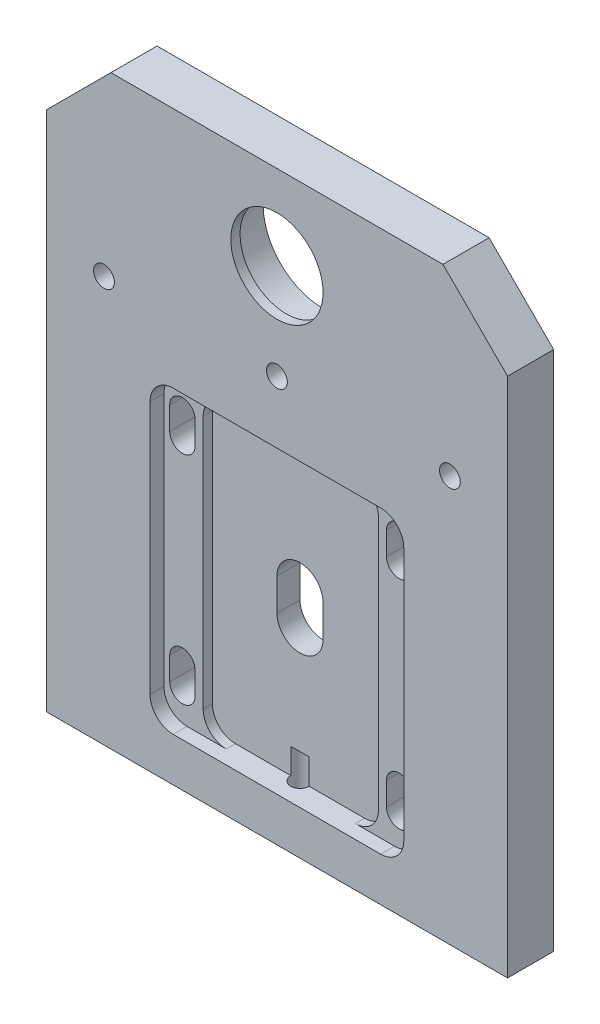
SolidWorks part; units mm, degrees
ref_plane "Piano frontale" through (0, 0, 0) normal (0, 0, 1) x (1, 0, 0)
ref_plane "Piano superiore" through (0, 0, 0) normal (0, 1, 0) x (1, 0, 0)
ref_plane "Piano destro" through (0, 0, 0) normal (1, 0, 0) x (0, 0, -1)
sketch "Schizzo1" plane through (0, 0, 0) normal (0, 0, 1) x (1, 0, 0)
  line L0 (0, 113) -> (14, 127)
  line L1 (0, 0) -> (100, 0)
  line L2 (0, 0) -> (0, 113)
  line L3 (14, 127) -> (86, 127)
  line L4 (100, 0) -> (100, 113)
  line L5 (86, 127) -> (100, 113)
  point P1 (100, 127)
  point P2 (0, 127)
  dimension "D1" = 127
  dimension "D2" = 100
extrude "Estrusione-Estrusione1" add sketch "Schizzo1" against normal blind 10
sketch "Schizzo2" plane through (0, 0, 0) normal (0, 0, 1) x (1, 0, 0)
  line L0 (86, 127) -> (14, 127) construction
  line L2 (50, 0) -> (50, 127) construction
  line L3 (0, 0) -> (100, 0) construction
  circle A0 centre (50, 108.7) radius 10
  dimension "D2" = 20
  dimension "D1" = 18.3
extrude "Taglio-Estrusione1" cut sketch "Schizzo2" against normal blind 10
sketch "Schizzo3" plane through (0, 0, 0) normal (0, 0, 1) x (1, 0, 0)
  line L0 (86, 127) -> (14, 127) construction
  line L1 (95, 88) -> (0, 88) construction
  line L2 (0, 0) -> (100, 0) construction
  line L3 (0, 113) -> (0, 0) construction
  line L6 (50, 0) -> (50, 127) construction
  circle A0 centre (12.5, 88) radius 2.25
  circle A1 centre (50, 88) radius 2.25
  circle A2 centre (87.5, 88) radius 2.25
  dimension "D5" = 4.5
  dimension "D1" = 37.5
  dimension "D2" = 88
extrude "Taglio-Estrusione2" cut sketch "Schizzo3" against normal blind 10
sketch "Schizzo4" plane through (0, 0, 0) normal (0, 0, 1) x (1, 0, 0)
  line L0 (50, 0) -> (50, 127) construction
  line L1 (0, 0) -> (100, 0) construction
  line L2 (0, 88.7572) -> (0, -18.8818) construction
  line L3 (0, 113) -> (0, 0) construction
  line L4 (86, 127) -> (14, 127) construction
  line L8 (27.5, 74.5) -> (72.5, 74.5)
  line L9 (22.5, 69.5) -> (22.5, 14.5)
  line L10 (27.5, 9.5) -> (72.5, 9.5)
  line L11 (77.5, 69.5) -> (77.5, 14.5)
  arc A0 (22.5, 14.5) -> (27.5, 9.5) centre (27.5, 14.5) ccw
  arc A1 (72.5, 9.5) -> (77.5, 14.5) centre (72.5, 14.5) ccw
  arc A2 (77.5, 69.5) -> (72.5, 74.5) centre (72.5, 69.5) ccw
  arc A3 (27.5, 74.5) -> (22.5, 69.5) centre (27.5, 69.5) ccw
  point P23 (77.5, 9.5)
  point P28 (22.5, 74.5)
  dimension "D5" = 5
  dimension "D1" = 45
extrude "Taglio-Estrusione3" cut sketch "Schizzo4" against normal blind 3
sketch "Schizzo5" plane through (0, 0, -3) normal (0, 0, 1) x (1, 0, 0)
  line L0 (0, 0) -> (0, -14.3774) construction
  line L1 (50, 0) -> (50, 127) construction
  line L2 (0, 0) -> (100, 0) construction
  line L3 (86, 127) -> (14, 127) construction
  line L7 (27.5, 9.5) -> (72.5, 9.5) construction
  line L8 (36, 74.5) -> (64, 74.5)
  line L9 (31, 69.5) -> (31, 14.5)
  line L10 (36, 9.5) -> (64, 9.5)
  line L11 (69, 69.5) -> (69, 14.5)
  arc A0 (31, 14.5) -> (36, 9.5) centre (36, 14.5) ccw
  arc A1 (64, 9.5) -> (69, 14.5) centre (64, 14.5) ccw
  arc A2 (64, 74.5) -> (69, 69.5) centre (64, 69.5) cw
  arc A3 (36, 74.5) -> (31, 69.5) centre (36, 69.5) ccw
  point P21 (69, 9.5)
  dimension "D3" = 5
  dimension "D1" = 38
  dimension "D2" = 65
extrude "Taglio-Estrusione4" cut sketch "Schizzo5" against normal blind 2
sketch "Schizzo6" plane through (0, 0, -5) normal (0, 0, 1) x (1, 0, 0)
  line L0 (31, 42) -> (69, 42) construction
  line L1 (31, 69.5) -> (31, 14.5) construction
  line L2 (69, 14.5) -> (69, 69.5) construction
  line L3 (50, 74.5) -> (50, 9.5) construction
  line L4 (64, 74.5) -> (36, 74.5) construction
  line L5 (36, 9.5) -> (64, 9.5) construction
  line L6 (50, 45.5) -> (50, 38.5) construction
  line L13 (54.9932, 45.5) -> (54.9932, 38.5)
  line L14 (45.0068, 45.5) -> (45.0068, 38.5)
  arc A0 (54.9932, 45.5) -> (45.0068, 45.5) centre (50, 45.5) ccw
  arc A1 (45.0068, 38.5) -> (54.9932, 38.5) centre (50, 38.5) ccw
  point P12 (50, 42)
  point P19 (50, 42)
  dimension "D3" = 29
  dimension "D1" = 4.9932
  dimension "D2" = 7
  dimension "D4" = 4.9932
extrude "Taglio-Estrusione5" cut sketch "Schizzo6" against normal through all
sketch "Schizzo7" plane through (0, 0, -3) normal (0, 0, 1) x (1, 0, 0)
  line L0 (22.5, 42) -> (31, 42) construction
  line L1 (22.5, 69.5) -> (22.5, 14.5) construction
  line L2 (31, 69.5) -> (31, 14.5) construction
  line L3 (26.5, 63) -> (26.5, 68) construction
  line L4 (31, 42) -> (69, 42) construction
  line L5 (26.5, 65.5) -> (73.5, 65.5) construction
  line L6 (26.5, 65.5) -> (26.5, 18.5) construction
  line L7 (26.5, 18.5) -> (73.5, 18.5) construction
  line L8 (73.5, 65.5) -> (73.5, 18.5) construction
  line L9 (26.5, 65.5) -> (73.5, 18.5) construction
  line L10 (26.5, 18.5) -> (73.5, 65.5) construction
  line L11 (69, 14.5) -> (69, 69.5) construction
  line L12 (50, 42) -> (50, 0) construction
  line L13 (23.75, 63) -> (23.75, 68)
  line L14 (29.25, 63) -> (29.25, 68)
  line L15 (73.5, 63) -> (73.5, 68) construction
  line L16 (70.75, 63) -> (70.75, 68)
  line L17 (76.25, 63) -> (76.25, 68)
  line L18 (26.5, 16) -> (26.5, 21) construction
  line L19 (23.75, 16) -> (23.75, 21)
  line L20 (29.25, 16) -> (29.25, 21)
  line L21 (73.5, 16) -> (73.5, 21) construction
  line L22 (70.75, 16) -> (70.75, 21)
  line L23 (76.25, 16) -> (76.25, 21)
  line L24 (0, 0) -> (100, 0) construction
  arc A0 (23.75, 63) -> (29.25, 63) centre (26.5, 63) ccw
  arc A1 (29.25, 68) -> (23.75, 68) centre (26.5, 68) ccw
  arc A2 (70.75, 63) -> (76.25, 63) centre (73.5, 63) ccw
  arc A3 (76.25, 68) -> (70.75, 68) centre (73.5, 68) ccw
  arc A4 (23.75, 16) -> (29.25, 16) centre (26.5, 16) ccw
  arc A5 (29.25, 21) -> (23.75, 21) centre (26.5, 21) ccw
  arc A6 (70.75, 16) -> (76.25, 16) centre (73.5, 16) ccw
  arc A7 (76.25, 21) -> (70.75, 21) centre (73.5, 21) ccw
  point P8 (50, 42)
  point P18 (26.5, 65.5)
  point P25 (73.5, 65.5)
  point P31 (26.5, 18.5)
  point P38 (73.5, 18.5)
  dimension "D1" = 47
  dimension "D2" = 47
extrude "Taglio-Estrusione6" cut sketch "Schizzo7" against normal through all
sketch "Schizzo8" plane through (0, 0, -10) normal (0, 0, -1) x (-1, 0, 0)
  circle A0 centre (-50, 108.7) radius 13
  dimension "D1" = 26
extrude "Taglio-Estrusione7" cut sketch "Schizzo8" against normal blind 8
sketch "Schizzo9" plane through (0, 0, -10) normal (0, 0, -1) x (-1, 0, 0)
  circle A0 centre (-85, 83) radius 4
  circle A1 centre (-50, 88) radius 4
  circle A2 centre (-12.5, 88) radius 4
  dimension "D1" = 8
  dimension "D2" = 8
  dimension "D3" = 8
extrude "Taglio-Estrusione8" cut sketch "Schizzo9" against normal blind 4
sketch "Schizzo10" plane through (0, 0, 0) normal (0, -1, 0) x (1, 0, 0)
  line L0 (50, 0) -> (50, -10) construction
  line L4 (0, 0) -> (100, 0) construction
  line L9 (0, -10) -> (100, -10) construction
  line L10 (100, -5) -> (0, -5) construction
  line L11 (100, -10) -> (100, 0) construction
  circle A0 centre (50, -5) radius 2
  circle A1 centre (19.5, -5) radius 2
  circle A2 centre (80.5, -5) radius 2
  dimension "D1" = 4
  dimension "D2" = 4
  dimension "D3" = 30.5
extrude "Taglio-Estrusione9" cut sketch "Schizzo10" against normal blind 15
